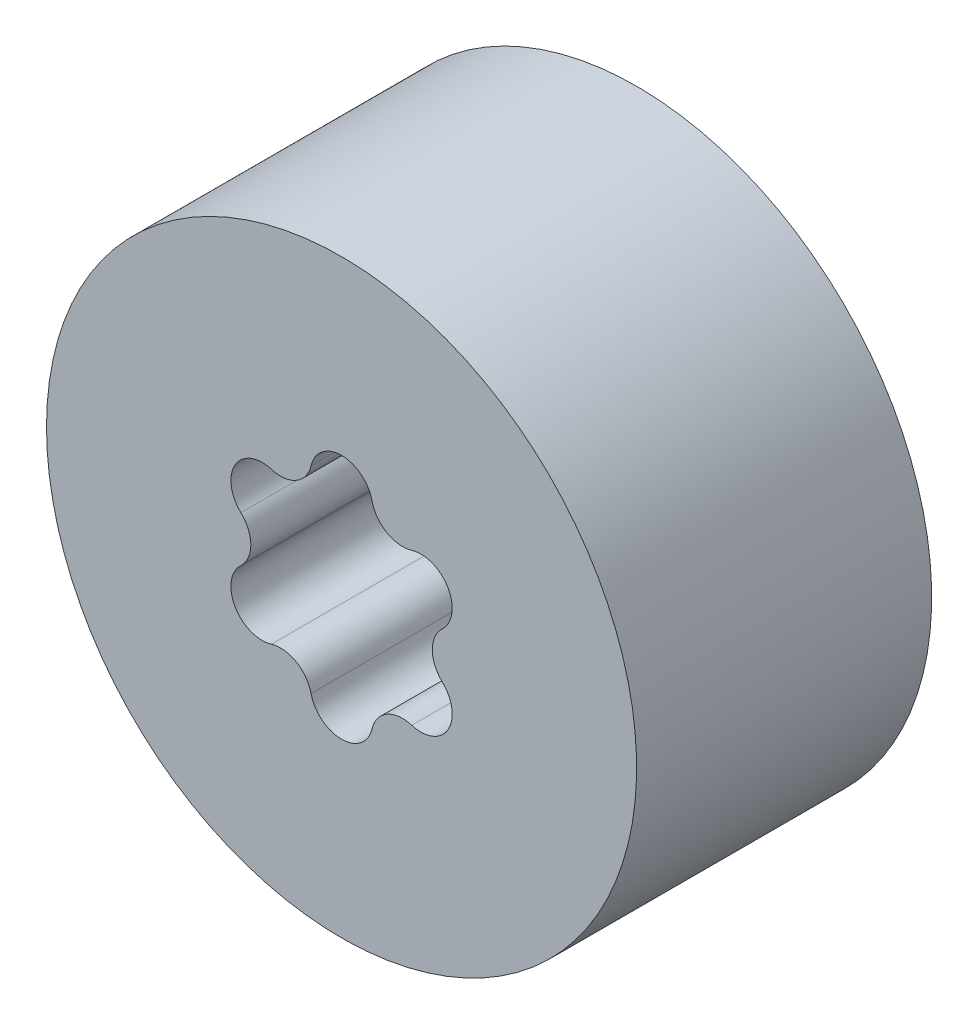
SolidWorks part; units mm, degrees
material "NEOPRENE"
ref_plane "Front Plane" through (0, 0, 0) normal (0, 0, 1) x (1, 0, 0)
ref_plane "Top Plane" through (0, 0, 0) normal (0, 1, 0) x (1, 0, 0)
ref_plane "Right Plane" through (0, 0, 0) normal (1, 0, 0) x (0, 0, -1)
sketch "Sketch1" plane through (0, 0, 0) normal (0, 0, 1) x (1, 0, 0)
  circle A0 centre (0, 0) radius 5
  circle A1 centre (0, 0) radius 19.05
  dimension "D1" = 10
  dimension "D2" = 38.1
extrude "Boss-Extrude1" add sketch "Sketch1" along normal mid plane 19.05
sketch "Sketch2" plane through (0, 0, -9.525) normal (0, 0, -1) x (-1, 0, 0)
  arc A12 (-1.9698, -6.3699) -> (-4.5316, -4.8909) centre (-3.9397, -6.8237) ccw
  arc A13 (-6.5014, -1.479) -> (-4.5316, -4.8909) centre (-5.1235, -2.958) ccw
  arc A14 (-6.5014, -1.479) -> (-6.5014, 1.479) centre (-7.8793, 0) ccw
  arc A15 (-4.5316, 4.8909) -> (-6.5014, 1.479) centre (-5.1235, 2.958) ccw
  arc A16 (-4.5316, 4.8909) -> (-1.9698, 6.3699) centre (-3.9397, 6.8237) ccw
  arc A17 (1.9698, 6.3699) -> (-1.9698, 6.3699) centre (0, 5.9161) ccw
  arc A18 (1.9698, 6.3699) -> (4.5316, 4.8909) centre (3.9397, 6.8237) ccw
  arc A19 (6.5014, 1.479) -> (4.5316, 4.8909) centre (5.1235, 2.958) ccw
  arc A20 (6.5014, 1.479) -> (6.5014, -1.479) centre (7.8793, 0) ccw
  arc A21 (4.5316, -4.8909) -> (6.5014, -1.479) centre (5.1235, -2.958) ccw
  arc A22 (4.5316, -4.8909) -> (1.9698, -6.3699) centre (3.9397, -6.8237) ccw
  arc A23 (-1.9698, -6.3699) -> (1.9698, -6.3699) centre (0, -5.9161) ccw
  arc A24 (-1.9698, -6.3699) -> (-4.5316, -4.8909) centre (-3.9397, -6.8237) ccw
  arc A25 (-6.5014, -1.479) -> (-4.5316, -4.8909) centre (-5.1235, -2.958) ccw
  arc A26 (-6.5014, -1.479) -> (-6.5014, 1.479) centre (-7.8793, 0) ccw
  arc A27 (-4.5316, 4.8909) -> (-6.5014, 1.479) centre (-5.1235, 2.958) ccw
  arc A28 (-4.5316, 4.8909) -> (-1.9698, 6.3699) centre (-3.9397, 6.8237) ccw
  arc A29 (1.9698, 6.3699) -> (-1.9698, 6.3699) centre (0, 5.9161) ccw
  arc A30 (1.9698, 6.3699) -> (4.5316, 4.8909) centre (3.9397, 6.8237) ccw
  arc A31 (6.5014, 1.479) -> (4.5316, 4.8909) centre (5.1235, 2.958) ccw
  arc A32 (6.5014, 1.479) -> (6.5014, -1.479) centre (7.8793, 0) ccw
  arc A33 (4.5316, -4.8909) -> (6.5014, -1.479) centre (5.1235, -2.958) ccw
  arc A34 (4.5316, -4.8909) -> (1.9698, -6.3699) centre (3.9397, -6.8237) ccw
  arc A35 (-1.9698, -6.3699) -> (1.9698, -6.3699) centre (0, -5.9161) ccw
  dimension "D1" = 0
extrude "Cut-Extrude1" cut sketch "Sketch2" against normal through all
